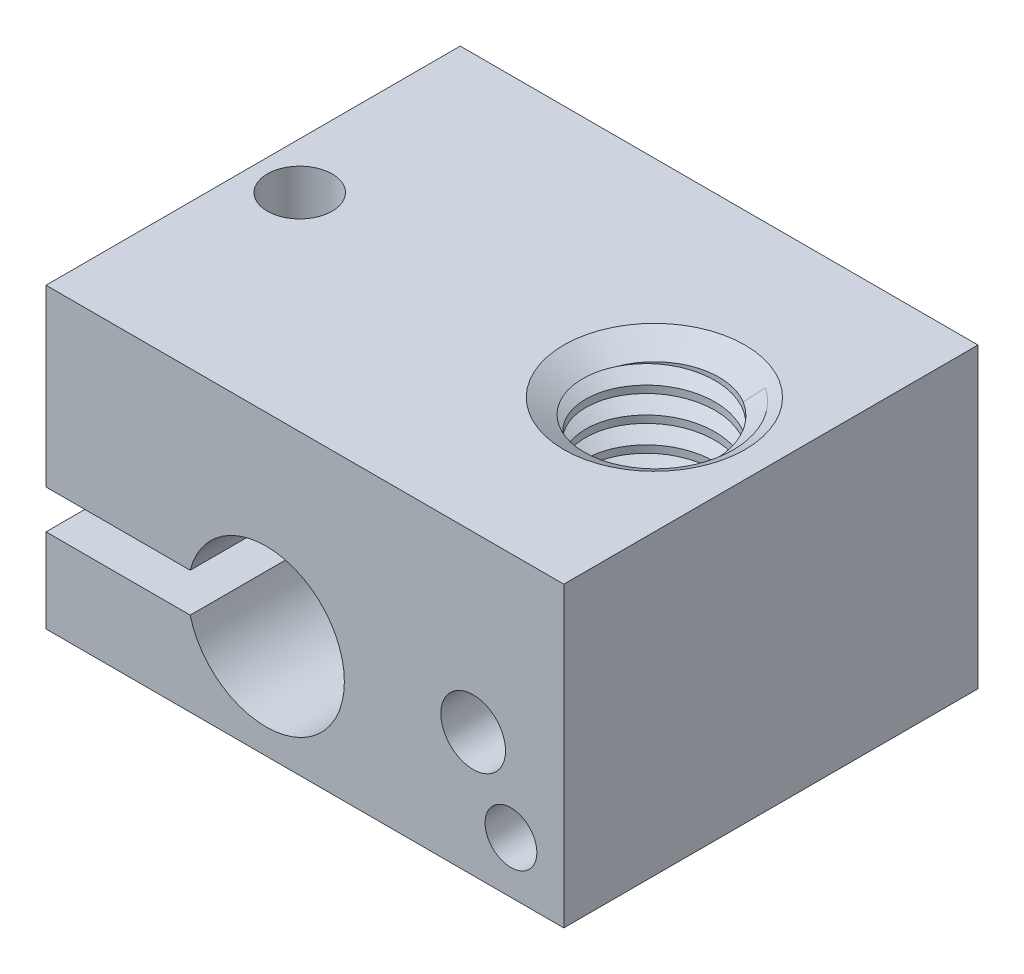
SolidWorks part; units mm, degrees
material "Copper"
ref_plane "Front Plane" through (0, 0, 0) normal (0, 0, 1) x (1, 0, 0)
ref_plane "Top Plane" through (0, 0, 0) normal (0, 1, 0) x (1, 0, 0)
ref_plane "Right Plane" through (0, 0, 0) normal (1, 0, 0) x (0, 0, -1)
sketch "Sketch1" plane through (0, 0, 0) normal (0, 1, 0) x (1, 0, 0)
  line L1 (10, 8) -> (-10, 8)
  line L2 (10, 8) -> (10, -8)
  line L3 (10, -8) -> (-10, -8)
  line L4 (-10, 8) -> (-10, -8)
  line L5 (10, 8) -> (-10, -8) construction
  line L6 (10, -8) -> (-10, 8) construction
  point P0 (0, 0)
  dimension "D1" = 20
  dimension "D2" = 16
extrude "Boss-Extrude1" add sketch "Sketch1" along normal mid plane 11.5
sketch "Sketch2" plane through (0, 5.75, 0) normal (0, 1, 0) x (1, 0, 0)
  line L0 (0, 8) -> (0, -8) construction
  line L1 (10, 8) -> (-10, 8) construction
  line L2 (-10, -8) -> (10, -8) construction
  line L3 (-10, 0) -> (10, 0) construction
  line L4 (-10, 8) -> (-10, -8) construction
  line L5 (10, -8) -> (10, 8) construction
  circle A0 centre (5.5, 0) radius 2.5
  circle A1 centre (-8.2, 0) radius 1.25
  dimension "D1" = 5
  dimension "D4" = 2.5
  dimension "D2" = 4.5
  dimension "D3" = 1.8
extrude "Cut-Extrude1" cut sketch "Sketch2" against normal up to next
sketch "Sketch3" plane through (0, 0, 8) normal (0, 0, 1) x (1, 0, 0)
  line L0 (0, 0) -> (-18.9264, 0) construction
  line L1 (-18.9264, 0) -> (-18.9264, -4.2761) construction
  line L2 (-18.9264, -4.2761) -> (0, -4.2761) construction
  line L3 (0, -4.2761) -> (0, 0) construction
  line L4 (0, -1.75) -> (-17.234, -1.75) construction
  line L5 (-10, -5.75) -> (10, -5.75) construction
  line L6 (-15.1475, -1.75) -> (-15.1475, -1)
  line L7 (-15.1475, -1) -> (-4.4306, -1)
  line L9 (-15.1475, -1.75) -> (-15.1475, -2.5)
  line L10 (-15.1475, -2.5) -> (-4.4306, -2.5)
  line L11 (10, 5.75) -> (10, -5.75) construction
  arc A0 (-4.4306, -1) -> (-4.4306, -2.5) centre (-1.5, -1.75) cw
  dimension "D2" = 3.025
  dimension "D1" = 4
  dimension "D3" = 11.5
  dimension "D4" = 0.75
  dimension "D5" = 0.75
extrude "Cut-Extrude2" cut sketch "Sketch3" against normal up to next
sketch "Sketch4" plane through (0, 0, 8) normal (0, 0, 1) x (1, 0, 0)
  line L0 (2.5543, -3.75) -> (13.3659, -3.75) construction
  line L1 (13.3659, -3.75) -> (13.3659, -0.95) construction
  line L2 (13.3659, -0.95) -> (5.608, -0.95) construction
  line L3 (-10, -5.75) -> (10, -5.75) construction
  line L4 (8, -5.75) -> (8, 1.0186) construction
  line L5 (8, 1.0186) -> (6.5, 1.0186) construction
  line L6 (6.5, 1.0186) -> (6.5, -5.75) construction
  line L7 (10, 5.75) -> (10, -5.75) construction
  circle A0 centre (7.9601, -3.75) radius 1
  circle A1 centre (6.5, -0.95) radius 1.25
  dimension "D5" = 2
  dimension "D6" = 2.5
  dimension "D1" = 2
  dimension "D2" = 4.8
  dimension "D3" = 2
  dimension "D4" = 3.5
extrude "Cut-Extrude3" cut sketch "Sketch4" against normal blind 3.4
sketch "Sketch5" plane through (0, 0, 8) normal (0, 0, 1) x (1, 0, 0)
  circle A0 centre (7.9601, -3.75) radius 0.8
  dimension "D1" = 1.6
extrude "Cut-Extrude4" cut sketch "Sketch5" against normal blind 4.4
ref_plane "Plane1" through (0, 8.75, 0) normal (0, 1, 0) x (1, 0, 0)
sketch "Sketch6" plane through (0, 8.75, 0) normal (0, 1, 0) x (1, 0, 0)
  circle A0 centre (5.5, 0) radius 2.5 construction
  circle A1 centre (5.5, 0) radius 2.5 construction
  circle A2 centre (5.5, 0) radius 3.125
  dimension "D1" = 6.25
curve "Helix/Spiral1" pitch 1 height 20 radius 3.125 centre (5.5, 8.75, 0) axis (0, -1, 0) start towards (0, 0, 1)
chamfer "Chamfer1" distance 1 angle 30 1 edges at (5.5, 5.75, 2.5) first distance on face at (-8.2, 5.75, 1.25)
sketch "Sketch7" plane through (0, 0, 0) normal (0, 0, 1) x (1, 0, 0)
  line L0 (8.6229, 6.3692) -> (6.1425, 6.3692) construction
  line L1 (8.6229, 6.3692) -> (7.7482, 6.8742)
  line L2 (7.7482, 6.8742) -> (7.7482, 5.8642)
  line L3 (8.6229, 6.3692) -> (7.7482, 5.8642)
  spline S0 degree 3 poles (3.2903, 8.75) (3.5777, 8.7293) (4.2738, 8.6874) (5.4998, 8.625) (6.7271, 8.5625) (7.7672, 8.5) (8.4623, 8.4375) (8.7064, 8.375) (8.4623, 8.3125) (7.7672, 8.25) (6.727, 8.1875) (5.5, 8.125) (4.273, 8.0625) (3.2328, 8) (2.5377, 7.9375) (2.2936, 7.875) (2.5377, 7.8125) (3.2328, 7.75) (4.273, 7.6875) (5.5, 7.625) (6.727, 7.5625) (7.7672, 7.5) (8.4623, 7.4375) (8.7064, 7.375) (8.4623, 7.3125) (7.7672, 7.25) (6.727, 7.1875) (5.5, 7.125) (4.273, 7.0625) (3.2328, 7) (2.5377, 6.9375) (2.2936, 6.875) (2.5377, 6.8125) (3.2328, 6.75) (4.273, 6.6875) (5.5, 6.625) (6.727, 6.5625) (7.7672, 6.5) (8.4623, 6.4375) (8.7064, 6.375) (8.4623, 6.3125) (7.7672, 6.25) (6.727, 6.1875) (5.5, 6.125) (4.273, 6.0625) (3.2328, 6) (2.5377, 5.9375) (2.2936, 5.875) (2.5377, 5.8125) (3.2328, 5.75) (4.273, 5.6875) (5.5, 5.625) (6.727, 5.5625) (7.7672, 5.5) (8.4623, 5.4375) (8.7064, 5.375) (8.4623, 5.3125) (7.7672, 5.25) (6.727, 5.1875) (5.5, 5.125) (4.273, 5.0625) (3.2328, 5) (2.5377, 4.9375) (2.2936, 4.875) (2.5377, 4.8125) (3.2328, 4.75) (4.273, 4.6875) (5.5, 4.625) (6.727, 4.5625) (7.7672, 4.5) (8.4623, 4.4375) (8.7064, 4.375) (8.4623, 4.3125) (7.7672, 4.25) (6.727, 4.1875) (5.5, 4.125) (4.273, 4.0625) (3.2328, 4) (2.5377, 3.9375) (2.2936, 3.875) (2.5377, 3.8125) (3.2328, 3.75) (4.273, 3.6875) (5.5, 3.625) (6.727, 3.5625) (7.7672, 3.5) (8.4623, 3.4375) (8.7064, 3.375) (8.4623, 3.3125) (7.7672, 3.25) (6.727, 3.1875) (5.5, 3.125) (4.273, 3.0625) (3.2328, 3) (2.5377, 2.9375) (2.2936, 2.875) (2.5377, 2.8125) (3.2328, 2.75) (4.273, 2.6875) (5.5, 2.625) (6.727, 2.5625) (7.7672, 2.5) (8.4623, 2.4375) (8.7064, 2.375) (8.4623, 2.3125) (7.7672, 2.25) (6.727, 2.1875) (5.5, 2.125) (4.273, 2.0625) (3.2328, 2) (2.5377, 1.9375) (2.2936, 1.875) (2.5377, 1.8125) (3.2328, 1.75) (4.273, 1.6875) (5.5, 1.625) (6.727, 1.5625) (7.7672, 1.5) (8.4623, 1.4375) (8.7064, 1.375) (8.4623, 1.3125) (7.7672, 1.25) (6.727, 1.1875) (5.5, 1.125) (4.273, 1.0625) (3.2328, 1) (2.5377, 0.9375) (2.2936, 0.875) (2.5377, 0.8125) (3.2328, 0.75) (4.273, 0.6875) (5.5, 0.625) (6.727, 0.5625) (7.7672, 0.5) (8.4623, 0.4375) (8.7064, 0.375) (8.4623, 0.3125) (7.7672, 0.25) (6.727, 0.1875) (5.5, 0.125) (4.273, 0.0625) (3.2328, 0) (2.5377, -0.0625) (2.2936, -0.125) (2.5377, -0.1875) (3.2328, -0.25) (4.273, -0.3125) (5.5, -0.375) (6.727, -0.4375) (7.7672, -0.5) (8.4623, -0.5625) (8.7064, -0.625) (8.4623, -0.6875) (7.7672, -0.75) (6.727, -0.8125) (5.5, -0.875) (4.273, -0.9375) (3.2328, -1) (2.5377, -1.0625) (2.2936, -1.125) (2.5377, -1.1875) (3.2328, -1.25) (4.273, -1.3125) (5.5, -1.375) (6.727, -1.4375) (7.7672, -1.5) (8.4623, -1.5625) (8.7064, -1.625) (8.4623, -1.6875) (7.7672, -1.75) (6.727, -1.8125) (5.5, -1.875) (4.273, -1.9375) (3.2328, -2) (2.5377, -2.0625) (2.2936, -2.125) (2.5377, -2.1875) (3.2328, -2.25) (4.273, -2.3125) (5.5, -2.375) (6.727, -2.4375) (7.7672, -2.5) (8.4623, -2.5625) (8.7064, -2.625) (8.4623, -2.6875) (7.7672, -2.75) (6.727, -2.8125) (5.5, -2.875) (4.273, -2.9375) (3.2328, -3) (2.5377, -3.0625) (2.2936, -3.125) (2.5377, -3.1875) (3.2328, -3.25) (4.273, -3.3125) (5.5, -3.375) (6.727, -3.4375) (7.7672, -3.5) (8.4623, -3.5625) (8.7064, -3.625) (8.4623, -3.6875) (7.7672, -3.75) (6.727, -3.8125) (5.5, -3.875) (4.273, -3.9375) (3.2328, -4) (2.5377, -4.0625) (2.2936, -4.125) (2.5377, -4.1875) (3.2328, -4.25) (4.273, -4.3125) (5.5, -4.375) (6.727, -4.4375) (7.7672, -4.5) (8.4623, -4.5625) (8.7064, -4.625) (8.4623, -4.6875) (7.7672, -4.75) (6.727, -4.8125) (5.5, -4.875) (4.273, -4.9375) (3.2328, -5) (2.5377, -5.0625) (2.2936, -5.125) (2.5377, -5.1875) (3.2328, -5.25) (4.273, -5.3125) (5.5, -5.375) (6.727, -5.4375) (7.7672, -5.5) (8.4623, -5.5625) (8.7064, -5.625) (8.4623, -5.6875) (7.7672, -5.75) (6.727, -5.8125) (5.5, -5.875) (4.273, -5.9375) (3.2328, -6) (2.5377, -6.0625) (2.2936, -6.125) (2.5377, -6.1875) (3.2328, -6.25) (4.273, -6.3125) (5.5, -6.375) (6.727, -6.4375) (7.7672, -6.5) (8.4623, -6.5625) (8.7064, -6.625) (8.4623, -6.6875) (7.7672, -6.75) (6.727, -6.8125) (5.5, -6.875) (4.273, -6.9375) (3.2328, -7) (2.5377, -7.0625) (2.2936, -7.125) (2.5377, -7.1875) (3.2328, -7.25) (4.273, -7.3125) (5.5, -7.375) (6.727, -7.4375) (7.7672, -7.5) (8.4623, -7.5625) (8.7064, -7.625) (8.4623, -7.6875) (7.7672, -7.75) (6.727, -7.8125) (5.5, -7.875) (4.273, -7.9375) (3.2328, -8) (2.5377, -8.0625) (2.2936, -8.125) (2.5377, -8.1875) (3.2328, -8.25) (4.273, -8.3125) (5.5, -8.375) (6.727, -8.4375) (7.7672, -8.5) (8.4623, -8.5625) (8.7064, -8.625) (8.4623, -8.6875) (7.7672, -8.75) (6.727, -8.8125) (5.5, -8.875) (4.273, -8.9375) (3.2328, -9) (2.5377, -9.0625) (2.2936, -9.125) (2.5377, -9.1875) (3.2328, -9.25) (4.273, -9.3125) (5.5, -9.375) (6.727, -9.4375) (7.7672, -9.5) (8.4623, -9.5625) (8.7064, -9.625) (8.4623, -9.6875) (7.7672, -9.75) (6.727, -9.8125) (5.5, -9.875) (4.273, -9.9375) (3.2328, -10) (2.5377, -10.0625) (2.2936, -10.125) (2.5377, -10.1875) (3.2328, -10.25) (4.273, -10.3125) (5.5, -10.375) (6.727, -10.4375) (7.7672, -10.5) (8.4623, -10.5625) (8.7064, -10.625) (8.4623, -10.6875) (7.7672, -10.75) (6.727, -10.8125) (5.5, -10.875) (4.273, -10.9375) (3.2328, -11) (2.5377, -11.0625) (2.2939, -11.125) (2.5369, -11.1874) (3.0029, -11.2293) (3.2903, -11.25) knots 0 0 0 0 0.003125 0.00625 0.009375 0.0125 0.015625 0.01875 0.021875 0.025 0.028125 0.03125 0.034375 0.0375 0.040625 0.04375 0.046875 0.05 0.053125 0.05625 0.059375 0.0625 0.065625 0.06875 0.071875 0.075 0.078125 0.08125 0.084375 0.0875 0.090625 0.09375 0.096875 0.1 0.103125 0.10625 0.109375 0.1125 0.115625 0.11875 0.121875 0.125 0.128125 0.13125 0.134375 0.1375 0.140625 0.14375 0.146875 0.15 0.153125 0.15625 0.159375 0.1625 0.165625 0.16875 0.171875 0.175 0.178125 0.18125 0.184375 0.1875 0.190625 0.19375 0.196875 0.2 0.203125 0.20625 0.209375 0.2125 0.215625 0.21875 0.221875 0.225 0.228125 0.23125 0.234375 0.2375 0.240625 0.24375 0.246875 0.25 0.253125 0.25625 0.259375 0.2625 0.265625 0.26875 0.271875 0.275 0.278125 0.28125 0.284375 0.2875 0.290625 0.29375 0.296875 0.3 0.303125 0.30625 0.309375 0.3125 0.315625 0.31875 0.321875 0.325 0.328125 0.33125 0.334375 0.3375 0.340625 0.34375 0.346875 0.35 0.353125 0.35625 0.359375 0.3625 0.365625 0.36875 0.371875 0.375 0.378125 0.38125 0.384375 0.3875 0.390625 0.39375 0.396875 0.4 0.403125 0.40625 0.409375 0.4125 0.415625 0.41875 0.421875 0.425 0.428125 0.43125 0.434375 0.4375 0.440625 0.44375 0.446875 0.45 0.453125 0.45625 0.459375 0.4625 0.465625 0.46875 0.471875 0.475 0.478125 0.48125 0.484375 0.4875 0.490625 0.49375 0.496875 0.5 0.503125 0.50625 0.509375 0.5125 0.515625 0.51875 0.521875 0.525 0.528125 0.53125 0.534375 0.5375 0.540625 0.54375 0.546875 0.55 0.553125 0.55625 0.559375 0.5625 0.565625 0.56875 0.571875 0.575 0.578125 0.58125 0.584375 0.5875 0.590625 0.59375 0.596875 0.6 0.603125 0.60625 0.609375 0.6125 0.615625 0.61875 0.621875 0.625 0.628125 0.63125 0.634375 0.6375 0.640625 0.64375 0.646875 0.65 0.653125 0.65625 0.659375 0.6625 0.665625 0.66875 0.671875 0.675 0.678125 0.68125 0.684375 0.6875 0.690625 0.69375 0.696875 0.7 0.703125 0.70625 0.709375 0.7125 0.715625 0.71875 0.721875 0.725 0.728125 0.73125 0.734375 0.7375 0.740625 0.74375 0.746875 0.75 0.753125 0.75625 0.759375 0.7625 0.765625 0.76875 0.771875 0.775 0.778125 0.78125 0.784375 0.7875 0.790625 0.79375 0.796875 0.8 0.803125 0.80625 0.809375 0.8125 0.815625 0.81875 0.821875 0.825 0.828125 0.83125 0.834375 0.8375 0.840625 0.84375 0.846875 0.85 0.853125 0.85625 0.859375 0.8625 0.865625 0.86875 0.871875 0.875 0.878125 0.88125 0.884375 0.8875 0.890625 0.89375 0.896875 0.9 0.903125 0.90625 0.909375 0.9125 0.915625 0.91875 0.921875 0.925 0.928125 0.93125 0.934375 0.9375 0.940625 0.94375 0.946875 0.95 0.953125 0.95625 0.959375 0.9625 0.965625 0.96875 0.971875 0.975 0.978125 0.98125 0.984375 0.9875 0.990625 0.99375 0.996875 1 1 1 1 construction
  point P7 (7.7482, 6.3692)
  dimension "D1" = 30
  dimension "D2" = 0.505
sweep "Cut-Sweep1" cut profiles "Sketch7" path "Helix/Spiral1"
